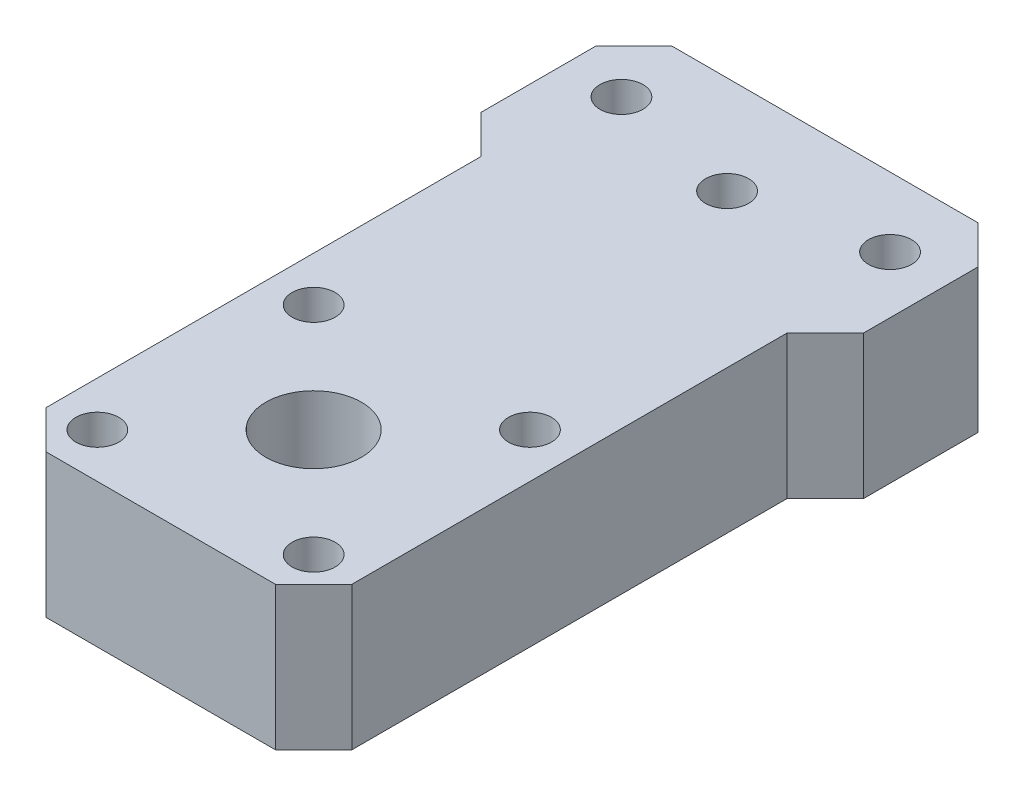
SolidWorks part; units mm, degrees
ref_plane "Front Plane" through (0, 0, 0) normal (0, 0, 1) x (1, 0, 0)
ref_plane "Top Plane" through (0, 0, 0) normal (0, 1, 0) x (1, 0, 0)
ref_plane "Right Plane" through (0, 0, 0) normal (1, 0, 0) x (0, 0, -1)
sketch "Sketch1" plane through (0, 0, 0) normal (0, 1, 0) x (1, 0, 0)
  line L0 (0, 53.5) -> (0, -16) construction
  line L1 (-11.3137, 11.3137) -> (11.3137, 11.3137) construction
  line L2 (-11.3137, 11.3137) -> (-11.3137, -11.3137) construction
  line L3 (-11.3137, -11.3137) -> (11.3137, -11.3137) construction
  line L4 (11.3137, 11.3137) -> (11.3137, -11.3137) construction
  line L5 (-11.3137, 11.3137) -> (11.3137, -11.3137) construction
  line L6 (-11.3137, -11.3137) -> (11.3137, 11.3137) construction
  line L7 (-16, -16) -> (16, -16)
  line L8 (-16, -16) -> (-16, 53.5)
  line L9 (-16, 53.5) -> (16, 53.5)
  line L10 (16, -16) -> (16, 53.5)
  circle A0 centre (0, 0) radius 5
  circle A1 centre (11.3137, -11.3137) radius 2.25
  circle A2 centre (11.3137, 11.3137) radius 2.25
  circle A3 centre (-11.3137, 11.3137) radius 2.25
  circle A4 centre (-11.3137, -11.3137) radius 2.25
  circle A5 centre (0, 0) radius 16 construction
  dimension "D2" = 10
  dimension "D3" = 4.5
  dimension "D1" = 32
  dimension "D4" = 16
  dimension "D5" = 32
  dimension "D6" = 53.5
extrude "Boss-Extrude1" add sketch "Sketch1" along normal blind 15
sketch "Sketch3" plane through (0, 0, 0) normal (0, 1, 0) x (1, 0, 0)
  line L1 (-35.5, 1.5) -> (-16, 1.5)
  line L2 (-35.5, 1.5) -> (-35.5, -1.5)
  line L3 (-35.5, -1.5) -> (-16, -1.5)
  line L4 (-16, 1.5) -> (-16, -1.5)
  line L5 (-35.5, 1.5) -> (-16, -1.5) construction
  line L6 (-35.5, -1.5) -> (-16, 1.5) construction
  line L8 (0, 0) -> (-25.75, 0) construction
  line L10 (-16, 53.5) -> (-16, -16) construction
  point P0 (-25.75, 0)
  dimension "D1" = 3
  dimension "D2" = 19.5
extrude "Boss-Extrude5" [suppressed] add sketch "Sketch3" along normal blind 15 contours L3 L4 L1 L2
sketch "Sketch4" plane through (0, 0, 0) normal (0, 0, 1) x (1, 0, 0)
  circle A0 centre (-26, 7.5) radius 4.5
  dimension "D3" = 9
  dimension "D1" = 7.5
  dimension "D2" = 26
extrude "Cut-Extrude1" [suppressed] cut sketch "Sketch4" against normal through all both and the other way through all
sketch "Sketch7" plane through (0, 0, 0) normal (0, 1, 0) x (1, 0, 0)
  line L0 (0, 53.5) -> (0, 37.5) construction
  line L1 (16, 53.5) -> (-16, 53.5) construction
  line L3 (-20, 53.5) -> (20, 53.5)
  line L4 (-20, 53.5) -> (-20, 37.5)
  line L5 (-20, 37.5) -> (20, 37.5)
  line L6 (20, 53.5) -> (20, 37.5)
  line L7 (-20, 53.5) -> (20, 37.5) construction
  line L8 (-20, 37.5) -> (20, 53.5) construction
  point P5 (0, 45.5)
  dimension "D1" = 16
  dimension "D2" = 40
extrude "Boss-Extrude6" add sketch "Sketch7" along normal blind 15
sketch "Sketch5" plane through (0, 0, 0) normal (0, 1, 0) x (1, 0, 0)
  line L0 (-16, 37.5) -> (16, 37.5) construction
  line L1 (-16, 37.5) -> (-16, -16) construction
  line L2 (16, -16) -> (16, 37.5) construction
  line L3 (20, 53.5) -> (-20, 53.5) construction
  line L4 (0, 37.5) -> (0, 43.25) construction
  line L5 (-20, 37.5) -> (20, 37.5) construction
  line L6 (-14.05, 46.25) -> (14.05, 46.25) construction
  line L8 (0, 43.25) -> (0, 46.25) construction
  circle A0 centre (0, 43.25) radius 2.25
  circle A1 centre (14.05, 46.25) radius 2.25
  circle A2 centre (-14.05, 46.25) radius 2.25
  point P20 (0, 37.5)
  dimension "D2" = 4.5
  dimension "D1" = 16
  dimension "D3" = 5.75
  dimension "D4" = 8.75
  dimension "D5" = 40
  dimension "D6" = 5.95
extrude "Cut-Extrude2" cut sketch "Sketch5" along normal through all
chamfer "Chamfer1" distance 4 angle 45 6 edges at (16, 7.5, 16) (-16, 7.5, 16) (-16, 7.5, -37.5) (16, 7.5, -37.5) (20, 7.5, -53.5) (-20, 7.5, -53.5)
